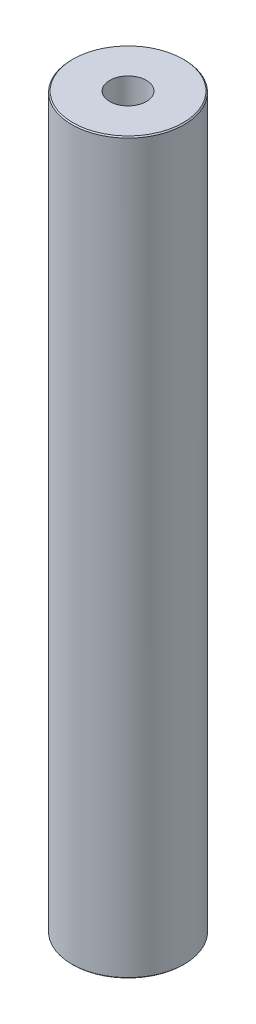
SolidWorks part; units mm, degrees
ref_plane "Front Plane" through (0, 0, 0) normal (0, 0, 1) x (1, 0, 0)
ref_plane "Top Plane" through (0, 0, 0) normal (0, 1, 0) x (1, 0, 0)
ref_plane "Right Plane" through (0, 0, 0) normal (1, 0, 0) x (0, 0, -1)
sketch "Sketch1" plane through (0, 0, 0) normal (0, 1, 0) x (1, 0, 0)
  circle A0 centre (0, 0) radius 32.5
  dimension "SHAFT_OD" = 65
extrude "Boss-Extrude1" add sketch "Sketch1" along normal blind 421.4377
sketch "Sketch2" plane through (0, 0, 0) normal (0, 1, 0) x (1, 0, 0)
  circle A0 centre (0, 0) radius 10.6083
  dimension "BORE_D" = 21.2167
extrude "Cut-Extrude1" cut sketch "Sketch2" along normal through all
chamfer "Chamfer1" distance 0.6434 angle 45 2 edges at (0, 421.4377, 32.5) (0, 0, 32.5)
